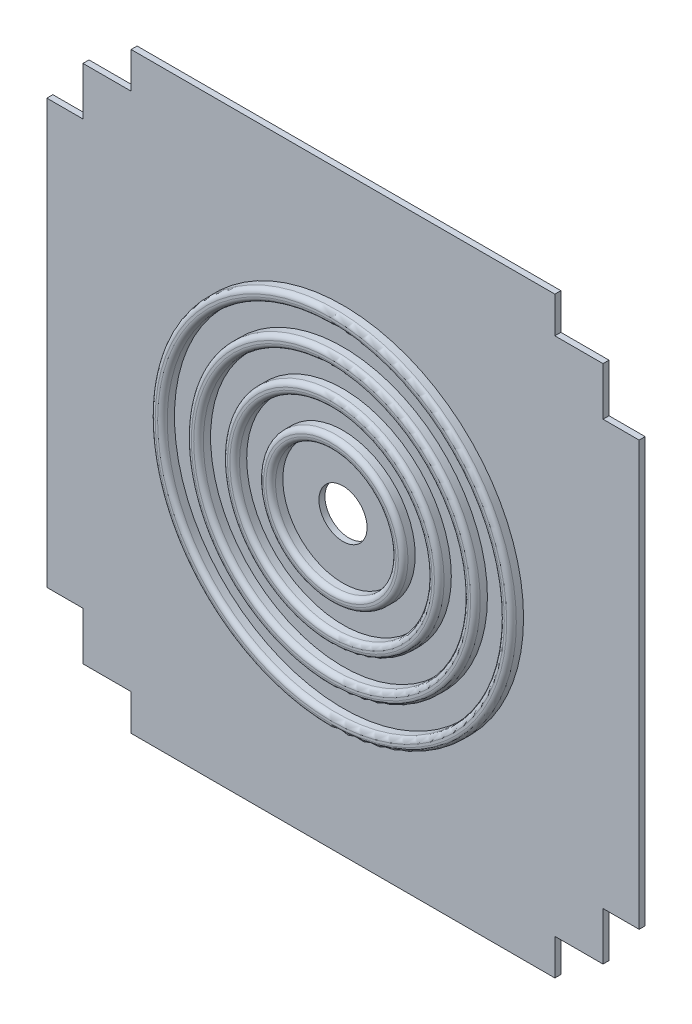
SolidWorks part; units mm, degrees
material "Acrílico (Impacto medio-alto)"
ref_plane "Alzado" through (0, 0, 0) normal (0, 0, 1) x (1, 0, 0)
ref_plane "Planta" through (0, 0, 0) normal (0, 1, 0) x (1, 0, 0)
ref_plane "Vista lateral" through (0, 0, 0) normal (1, 0, 0) x (0, 0, -1)
sketch "Croquis1" plane through (0, 0, 0) normal (0, 0, 1) x (1, 0, 0)
  line L0 (-246, 0) -> (246, 0)
  line L1 (0, 0) -> (0, 246) construction
  line L2 (-246, -176) -> (-246, 176)
  line L3 (-246, 176) -> (-216, 176)
  line L4 (-216, 176) -> (-216, 216)
  line L5 (-216, 216) -> (-176, 216)
  line L6 (-176, 216) -> (-176, 246)
  line L7 (-176, 246) -> (176, 246)
  line L8 (246, -176) -> (246, 176)
  line L9 (246, 176) -> (216, 176)
  line L10 (216, 176) -> (216, 216)
  line L11 (216, 216) -> (176, 216)
  line L12 (176, 216) -> (176, 246)
  line L13 (-246, -176) -> (-216, -176)
  line L14 (-216, -176) -> (-216, -216)
  line L15 (-216, -216) -> (-176, -216)
  line L16 (-176, -216) -> (-176, -246)
  line L17 (-176, -246) -> (176, -246)
  line L18 (176, -216) -> (176, -246)
  line L19 (216, -216) -> (176, -216)
  line L20 (216, -176) -> (216, -216)
  line L21 (246, -176) -> (216, -176)
  point P4 (0, 0)
  dimension "D1" = 492
  dimension "D2" = 176
  dimension "D3" = 216
  dimension "D4" = 176
  dimension "D5" = 30
  dimension "D6" = 40
extrude "Saliente-Extruir1" add sketch "Croquis1" along normal blind 5 contours L1 L0 L8 L9 L10 L11 L12 L7 | L0 L1 L7 L6 L5 L4 L3 L2 | L21 L8 L0 L2 L13 L14 L15 L16 L17 L18 L19 L20 region at (-117.505, 117.505, 0) region at (0, -117.505, 0) region at (117.505, 117.505, 0)
sketch "Croquis2" plane through (0, 0, 5) normal (0, 0, 1) x (1, 0, 0)
  circle A0 centre (0, 0) radius 20
  dimension "D1" = 40
extrude "Cortar-Extruir1" cut sketch "Croquis2" against normal blind 10
sketch "Croquis3" plane through (0, 0, 5) normal (0, 0, 1) x (1, 0, 0)
  circle A0 centre (0, 0) radius 50
  circle A1 centre (0, 0) radius 60
  circle A2 centre (0, 0) radius 120
  circle A3 centre (0, 0) radius 110
  circle A4 centre (0, 0) radius 80
  circle A5 centre (0, 0) radius 90
  circle A6 centre (0, 0) radius 150
  circle A7 centre (0, 0) radius 140
  dimension "D1" = 100
  dimension "D2" = 10
  dimension "D3" = 20
  dimension "D4" = 10
  dimension "D5" = 20
  dimension "D6" = 10
  dimension "D7" = 10
  dimension "D8" = 20
extrude "Saliente-Extruir2" add sketch "Croquis3" along normal blind 10 contours A1 A0 | A5 A4 | A2 A3 | A6 A7 region at (-58.3029, 0, 5) region at (-116.6059, 0, 5) region at (-87.4544, 0, 5) region at (-145.7574, 0, 5)
fillet "Redondeo1" radius 4 8 edges at (50, 0, 15) (60, 0, 15) (80, 0, 15) (90, 0, 15) (110, 0, 15) (120, 0, 15) (140, 0, 15) (150, 0, 15)
sketch "Croquis4" [suppressed] plane through (0, 0, 5) normal (0, 0, 1) x (1, 0, 0)
  circle A0 centre (0, 0) radius 140
  circle A1 centre (0, 0) radius 130
  circle A2 centre (0, 0) radius 110
  circle A3 centre (0, 0) radius 100
  circle A4 centre (0, 0) radius 80
  circle A5 centre (0, 0) radius 70
  circle A6 centre (0, 0) radius 50
  circle A7 centre (0, 0) radius 40
  circle A8 centre (0, 0) radius 140 construction
  circle A9 centre (0, 0) radius 110 construction
  circle A10 centre (0, 0) radius 80 construction
  circle A11 centre (0, 0) radius 50 construction
  dimension "D1" = 10
  dimension "D2" = 10
  dimension "D3" = 10
  dimension "D4" = 10
extrude "Saliente-Extruir3" [suppressed] add sketch "Croquis4" along normal blind 10 contours A0 A1 | A2 A3 | A4 A5 | A6 A7
fillet "Redondeo2" [suppressed] radius 4
